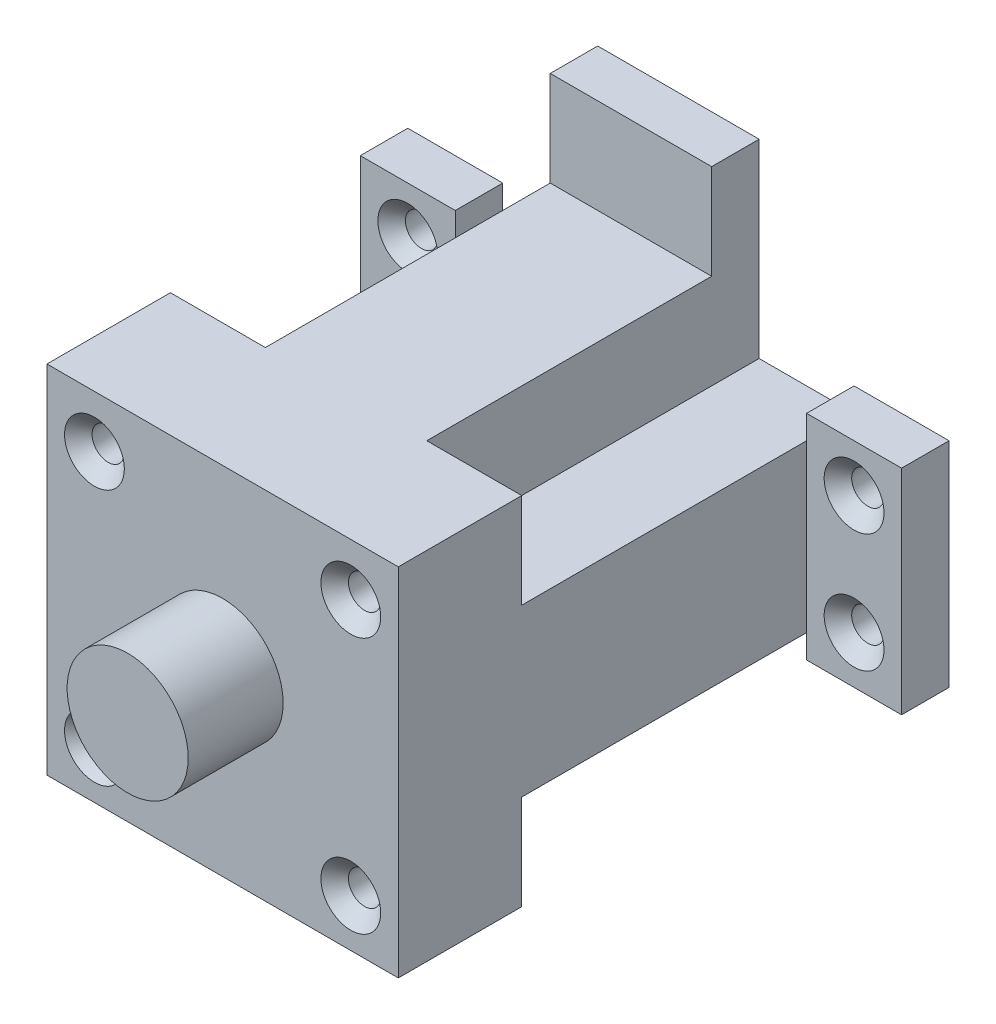
SolidWorks part; units mm, degrees
ref_plane "Plan de face" through (0, 0, 0) normal (0, 0, 1) x (1, 0, 0)
ref_plane "Plan de dessus" through (0, 0, 0) normal (0, 1, 0) x (1, 0, 0)
ref_plane "Plan de droite" through (0, 0, 0) normal (1, 0, 0) x (0, 0, -1)
sketch "Esquisse1" plane through (0, 0, 0) normal (0, 0, 1) x (1, 0, 0)
  line L2 (0, 0) -> (37, 0)
  line L3 (0, 0) -> (0, 37.5)
  line L4 (0, 37.5) -> (37, 37.5)
  line L5 (37, 0) -> (37, 37.5)
  dimension "D1" = 37.5
  dimension "D2" = 37
extrude "Boss.-Extru.1" add sketch "Esquisse1" along normal blind 48
sketch "Esquisse2" plane through (0, 0, 48) normal (0, 0, 1) x (1, 0, 0)
  line L0 (37, 0) -> (37, 37.5) construction
  line L4 (37, 37.5) -> (0, 37.5) construction
  circle A0 centre (18.5, 19) radius 6.375
  dimension "D3" = 12.75
  dimension "D1" = 18.5
  dimension "D2" = 18.5
extrude "Boss.-Extru.2" add sketch "Esquisse2" along normal blind 10
sketch "Esquisse3" plane through (0, 0, 48) normal (0, 0, 1) x (1, 0, 0)
  line L0 (37, 37.5) -> (0, 37.5) construction
  line L1 (0, 37.5) -> (0, 0) construction
  line L2 (37, 0) -> (37, 37.5) construction
  circle A0 centre (5, 32) radius 1.5
  circle A1 centre (32, 32) radius 1.5
  circle A2 centre (32, 5) radius 1.5
  circle A3 centre (5, 5) radius 1.5
  dimension "D3" = 3
  dimension "D5" = 3
  dimension "D9" = 3
  dimension "D11" = 3
  dimension "D1" = 5.5
  dimension "D2" = 5.5
  dimension "5" = 5
  dimension "D4" = 5
  dimension "D6" = 5
  dimension "D7" = 5
  dimension "D8" = 27
  dimension "D10" = 27
hole_wizard "Fraisage pour vis à tête fraisée bombée M31" positions "Esquisse4" profile "Esquisse5" countersink size "M3" standard "ISO"
sketch "Esquisse4" plane through (0, 0, 48) normal (0, 0, 1) x (1, 0, 0)
  point P0 (5, 32)
  point P3 (32, 32)
  point P6 (32, 5)
  point P9 (5, 5)
sketch "Esquisse5" plane through (5, 32, 48) normal (1, 0, 0) x (0, -1, 0)
  line L0 (0, 0) -> (0, 49.0215)
  line L1 (0, 49.0215) -> (1.7, 48)
  line L2 (1.7, 48) -> (1.7, 1.45)
  line L3 (1.7, 1.45) -> (3.15, 0)
  line L5 (3.15, 0) -> (0, 0)
  line L6 (-1.7, 1.45) -> (-3.15, 0) construction
  line L10 (0, 49.0215) -> (-1.7, 48) construction
  line L11 (0, -6.35) -> (0, 107.95) construction
  dimension "Diamètre du perçage" = 3.4
  dimension "Profondeur du perçage" = 48
  dimension "Diamètre du fraisage entrant" = 6.3
  dimension "Angle du fraisage entrant" = 90
  dimension "Angle de pointe" = 118
sketch "Esquisse6" plane through (0, 0, 0) normal (0, -1, 0) x (1, 0, 0)
  line L1 (0, 0) -> (10, 0)
  line L2 (0, 0) -> (0, 5)
  line L3 (0, 5) -> (10, 5)
  line L4 (10, 0) -> (10, 5)
  line L5 (37, 0) -> (27, 0)
  line L6 (37, 0) -> (37, 5)
  line L7 (37, 5) -> (27, 5)
  line L8 (27, 0) -> (27, 5)
  dimension "D1" = 10
  dimension "D2" = 5
  dimension "D3" = 10
  dimension "D4" = 5
extrude "Boss.-Extru.3" [suppressed] add sketch "Esquisse6" along normal blind 10
sketch "Esquisse7" plane through (0, 37.5, 0) normal (0, 1, 0) x (1, 0, 0)
  line L1 (0, 0) -> (10, 0)
  line L2 (0, 0) -> (0, -5)
  line L3 (0, -5) -> (10, -5)
  line L4 (10, 0) -> (10, -5)
  line L5 (37, 0) -> (27, 0)
  line L6 (37, 0) -> (37, -5)
  line L7 (37, -5) -> (27, -5)
  line L8 (27, 0) -> (27, -5)
  dimension "D1" = 5
  dimension "D2" = 5
  dimension "D3" = 10
  dimension "D4" = 10
extrude "Boss.-Extru.4" [suppressed] add sketch "Esquisse7" along normal blind 10
sketch "Esquisse8" [suppressed] plane through (0, 0, 5) normal (0, 0, 1) x (1, 0, 0)
  line L0 (37, -10) -> (27, -10) construction
  line L1 (37, -10) -> (37, 0) construction
  circle A0 centre (32, -5) radius 2.6226
  circle A1 centre (4.4036, -5.1811) radius 2.9344
  circle A2 centre (4.4036, 42.3532) radius 2.5459
  circle A3 centre (32.4325, 42.3532) radius 2.5419
  dimension "D1" = 5
  dimension "5" = 5
sketch "Esquisse10" plane through (0, 0, 0) normal (0, 0, -1) x (-1, 0, 0)
  line L1 (-37, 0) -> (-27, 0)
  line L2 (-37, 0) -> (-37, 10)
  line L3 (-37, 10) -> (-27, 10)
  line L4 (-27, 0) -> (-27, 10)
  line L5 (-37, 37.5) -> (-27, 37.5)
  line L6 (-37, 37.5) -> (-37, 27.5)
  line L7 (-37, 27.5) -> (-27, 27.5)
  line L8 (-27, 37.5) -> (-27, 27.5)
  line L9 (0, 37.5) -> (-10, 37.5)
  line L10 (0, 37.5) -> (0, 27.5)
  line L11 (0, 27.5) -> (-10, 27.5)
  line L12 (-10, 37.5) -> (-10, 27.5)
  line L13 (0, 0) -> (-10, 0)
  line L14 (0, 0) -> (0, 10)
  line L15 (0, 10) -> (-10, 10)
  line L16 (-10, 0) -> (-10, 10)
  dimension "D1" = 10
  dimension "D2" = 10
  dimension "D3" = 10
  dimension "D4" = 10
  dimension "D5" = 10
  dimension "D6" = 10
  dimension "10" = 10
  dimension "D7" = 10
extrude "Enlèv. mat.-Extru.1" cut sketch "Esquisse10" against normal blind 35
sketch "Esquisse11" plane through (0, 0, 0) normal (0, 0, -1) x (-1, 0, 0)
  line L0 (0, 37.5) -> (-10, 37.5) construction
  line L1 (-27, 37.5) -> (-10, 37.5)
  line L2 (-27, 37.5) -> (-27, 47.5)
  line L3 (-27, 47.5) -> (-10, 47.5)
  line L4 (-10, 37.5) -> (-10, 47.5)
  line L5 (-27, 37.5) -> (-10, 37.5) construction
  line L6 (-10, 37.5) -> (-10, 27.5) construction
  line L7 (-10, 37.5) -> (-10, 27.5) construction
  line L8 (0, 18.75) -> (-37, 18.75) construction
  line L9 (-37, 30) -> (-47, 30)
  line L10 (-37, 30) -> (-37, 7.5)
  line L11 (-37, 7.5) -> (-47, 7.5)
  line L12 (-47, 30) -> (-47, 7.5)
  line L13 (0, 30) -> (10, 30)
  line L14 (0, 30) -> (0, 7.5)
  line L15 (0, 7.5) -> (10, 7.5)
  line L16 (10, 30) -> (10, 7.5)
  line L21 (-37, 10) -> (-37, 27.5) construction
  line L22 (-47, 18.75) -> (-37, 18.75) construction
  line L23 (0, 18.75) -> (10, 18.75) construction
  line L24 (0, 27.5) -> (0, 10) construction
  point P23 (0, 0)
  point P29 (0, 0)
  point P32 (11.2968, 18.75)
  dimension "D1" = 10
  dimension "D2" = 10
  dimension "10" = 10
  dimension "D4" = 22.5
  dimension "D5" = 22.5
extrude "Boss.-Extru.5" add sketch "Esquisse11" against normal blind 5
sketch "Esquisse12" plane through (0, 0, 5) normal (0, 0, 1) x (1, 0, 0)
  line L1 (-10, 7.5) -> (-10, 30) construction
  line L4 (0, 7.5) -> (-10, 7.5) construction
  line L5 (-10, 30) -> (0, 30) construction
  line L9 (37, 30) -> (47, 30) construction
  line L10 (47, 30) -> (47, 7.5) construction
  line L11 (47, 7.5) -> (37, 7.5) construction
  circle A0 centre (-5, 12.5) radius 1.5
  circle A1 centre (-5, 25) radius 1.5
  circle A2 centre (42, 12.5) radius 1.5
  circle A3 centre (42, 25) radius 1.5
  point P20 (13.3506, 47.5)
  dimension "D5" = 3
  dimension "D6" = 3
  dimension "D11" = 3
  dimension "D13" = 3
  dimension "D1" = 5
  dimension "D2" = 5
  dimension "D3" = 5
  dimension "D4" = 5
  dimension "D10" = 5
  dimension "D12" = 5
  dimension "D14" = 5
  dimension "D15" = 5
hole_wizard "Fraisage pour vis à tête fraisée bombée M32" positions "Esquisse13" profile "Esquisse14" countersink size "M3" standard "ISO"
sketch "Esquisse13" plane through (0, 0, 5) normal (0, 0, 1) x (1, 0, 0)
  point P0 (-5, 12.5)
  point P3 (-5, 25)
  point P9 (42, 25)
  point P12 (42, 12.5)
  point P16 (0, 0)
sketch "Esquisse14" plane through (-5, 12.5, 5) normal (1, 0, 0) x (0, -1, 0)
  line L0 (0, 0) -> (0, 6.0215)
  line L1 (0, 6.0215) -> (1.7, 5)
  line L2 (1.7, 5) -> (1.7, 1.45)
  line L3 (1.7, 1.45) -> (3.15, 0)
  line L5 (3.15, 0) -> (0, 0)
  line L6 (-1.7, 1.45) -> (-3.15, 0) construction
  line L10 (0, 6.0215) -> (-1.7, 5) construction
  line L11 (0, -6.35) -> (0, 107.95) construction
  dimension "Diamètre du perçage" = 3.4
  dimension "Profondeur du perçage" = 5
  dimension "Diamètre du fraisage entrant" = 6.3
  dimension "Angle du fraisage entrant" = 90
  dimension "Angle de pointe" = 118
